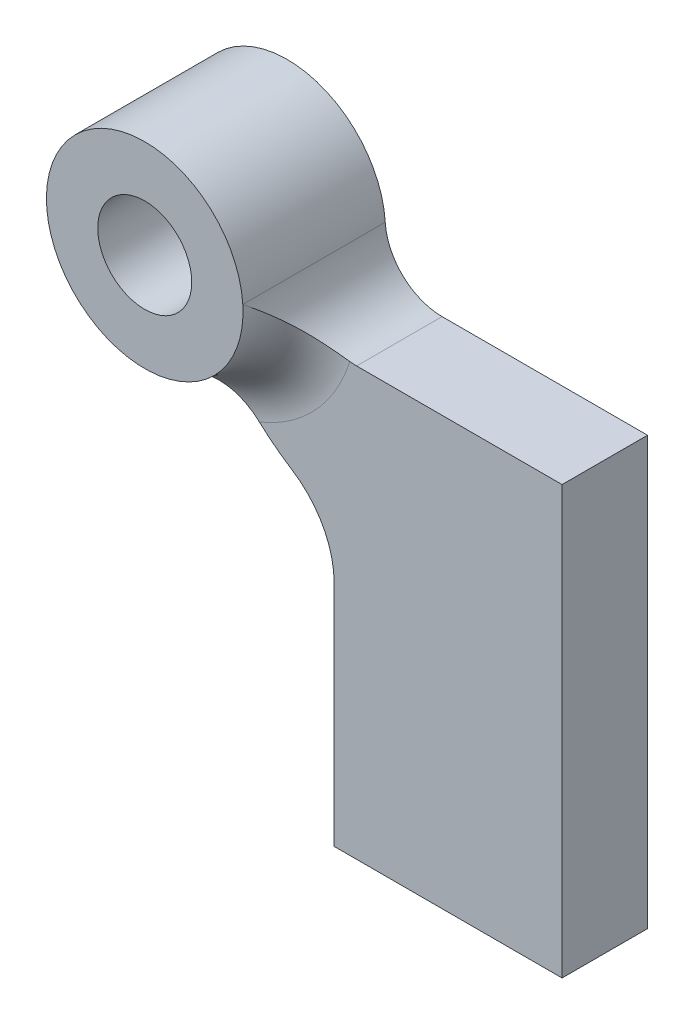
SolidWorks part; units mm, degrees
ref_plane "Front Plane" through (0, 0, 0) normal (0, 0, 1) x (1, 0, 0)
ref_plane "Top Plane" through (0, 0, 0) normal (0, 1, 0) x (1, 0, 0)
ref_plane "Right Plane" through (0, 0, 0) normal (1, 0, 0) x (0, 0, -1)
sketch "Sketch1" plane through (0, 0, 0) normal (0, 0, 1) x (1, 0, 0)
  circle A0 centre (0, 0) radius 1.65
  circle A1 centre (0, 0) radius 3.45
  dimension "D1" = 3.3
  dimension "D2" = 1.8
extrude "Boss-Extrude1" add sketch "Sketch1" along normal blind 5
sketch "Sketch2" plane through (0, 0, 0) normal (0, 0, -1) x (-1, 0, 0)
  line L0 (0, 0) -> (-1.65, 0) construction
  line L1 (-1.65, 0) -> (-1.65, -1.65) construction
  line L2 (-1.65, -1.65) -> (0, -1.65) construction
  line L3 (-1.65, -1.65) -> (0, 0) construction
  line L4 (0, -1.65) -> (0, 0) construction
  line L6 (-1.65, -1.65) -> (-12.65, -1.65)
  line L7 (-1.65, -1.65) -> (-1.65, -16.65)
  line L8 (-1.65, -16.65) -> (-12.65, -16.65)
  line L9 (-12.65, -1.65) -> (-12.65, -16.65)
  circle A0 centre (0, 0) radius 1.65 construction
  dimension "D1" = 11
  dimension "D2" = 15
extrude "Boss-Extrude2" add sketch "Sketch2" against normal blind 3
fillet "Fillet1" radius 2 3 edges at (3.0299, -1.65, 1.5) (1.65, -3.0299, 1.5) (2.4395, -2.4395, 3)
sketch "Sketch3" plane through (0, 0, 0) normal (0, 0, -1) x (-1, 0, 0)
  line L0 (-4.65, -16.65) -> (-4.65, -8.65)
  line L1 (-1.65, -16.65) -> (-12.65, -16.65) construction
  line L2 (-12.65, -1.65) -> (-12.65, -16.65) construction
  line L3 (-4.65, -16.65) -> (-1.65, -16.65)
  line L4 (-1.65, -16.65) -> (-1.65, -5.4387)
  arc A0 (-4.65, -8.65) -> (-1.65, -5.4387) centre (-1.4313, -8.65) cw
  dimension "D1" = 8
  dimension "D2" = 8
extrude "Cut-Extrude1" cut sketch "Sketch3" against normal through all
fillet "Fillet2" radius 8 1 edges at (1.65, -5.4387, 1.5)
